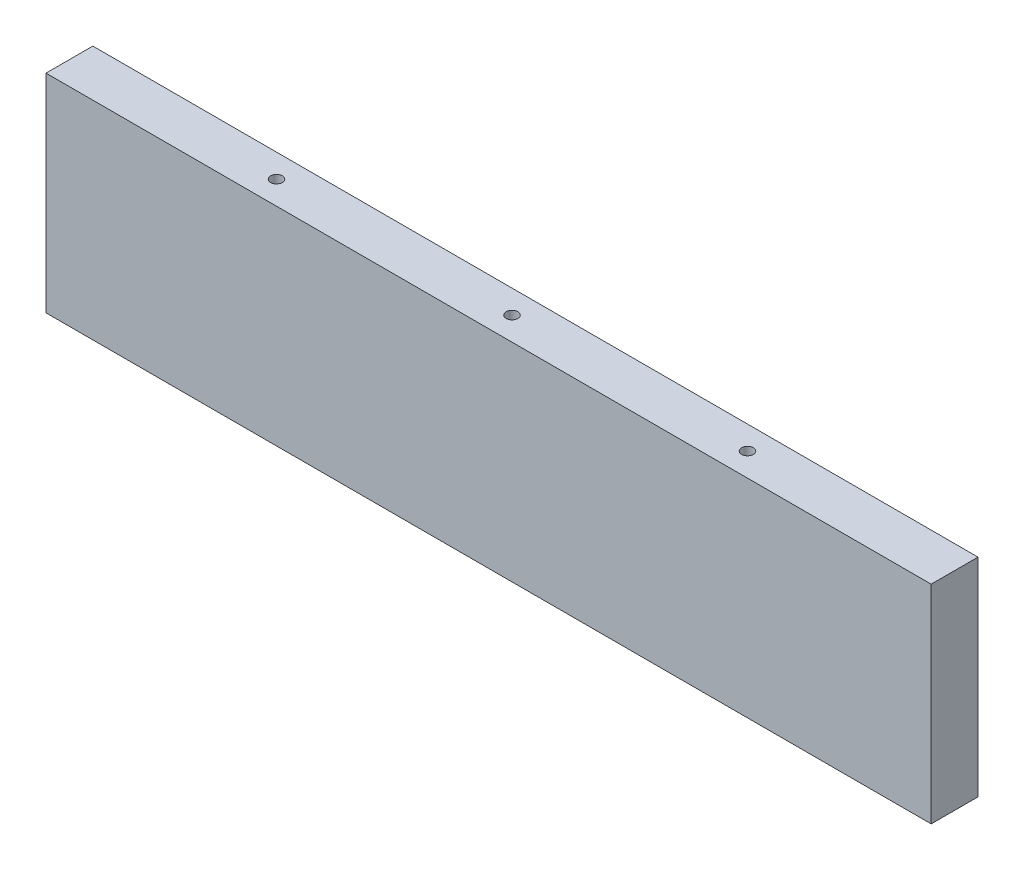
SolidWorks part; units mm, degrees
material "Beech"
ref_plane "Front Plane" through (0, 0, 0) normal (0, 0, 1) x (1, 0, 0)
ref_plane "Top Plane" through (0, 0, 0) normal (0, 1, 0) x (1, 0, 0)
ref_plane "Right Plane" through (0, 0, 0) normal (1, 0, 0) x (0, 0, -1)
sketch "Sketch1" plane through (0, 0, 0) normal (0, 0, 1) x (1, 0, 0)
  line L1 (-16.7045, 12.7) -> (-231.3045, 12.7)
  line L2 (-16.7045, 12.7) -> (-16.7045, 69)
  line L3 (-16.7045, 69) -> (-231.3045, 69)
  line L4 (-231.3045, 12.7) -> (-231.3045, 69)
  line L5 (-16.7045, 12.7) -> (-16.7045, 0) construction
  dimension "D1" = 56.3
extrude "Boss-Extrude1" add sketch "Sketch1" against normal blind 12.7
sketch "Sketch3" plane through (-231.3045, 0, 0) normal (-1, 0, 0) x (0, 0, 1)
  line L4 (0, 12.7) -> (0, 69)
  line L5 (0, 69) -> (-12.7, 69)
  line L6 (-12.7, 69) -> (-12.7, 12.7)
  line L7 (-12.7, 12.7) -> (0, 12.7)
  line L8 (0, 12.7) -> (0, 69)
  line L9 (0, 69) -> (-12.7, 69)
  line L10 (-12.7, 69) -> (-12.7, 12.7)
  line L11 (-12.7, 12.7) -> (0, 12.7)
  dimension "D1" = 0
extrude "Boss-Extrude2" add sketch "Sketch3" along normal blind 12.7
sketch "Sketch4" plane through (-16.7045, 0, 0) normal (1, 0, 0) x (0, 0, -1)
  line L4 (0, 69) -> (0, 12.7)
  line L5 (0, 12.7) -> (12.7, 12.7)
  line L6 (12.7, 12.7) -> (12.7, 69)
  line L7 (12.7, 69) -> (0, 69)
  line L8 (0, 69) -> (0, 12.7)
  line L9 (0, 12.7) -> (12.7, 12.7)
  line L10 (12.7, 12.7) -> (12.7, 69)
  line L11 (12.7, 69) -> (0, 69)
  dimension "D1" = 0
extrude "Boss-Extrude3" add sketch "Sketch4" along normal blind 12.7
hole_wizard "Hole2" positions "Sketch7" profile "Sketch8" legacy
sketch "Sketch7" plane through (-124.0045, 88.05, 66.1243) normal (0, 1, 0) x (1, 0, 0)
  point P15 (-162.3, -97.5257)
  point P34 (-113.65, -38.7424)
  point P36 (-113.65, 13.691)
  point P54 (162.3, -97.5257)
  point P55 (113.65, -38.7424)
  point P56 (113.65, 13.691)
  point P71 (63.85, 72.4743)
  point P73 (0, 72.4743)
  point P74 (-63.85, 72.4743)
sketch "Sketch8" plane through (-286.3045, 88.05, 163.65) normal (1, 0, 0) x (0, 0, 1)
  line L0 (0, 0) -> (0, 32.7039)
  line L1 (0, 32.7039) -> (1.5875, 31.75)
  line L2 (1.5875, 31.75) -> (1.5875, 4.0177)
  line L3 (1.5875, 4.0177) -> (5.08, 0)
  line L4 (5.08, 0) -> (0, 0)
  line L5 (0, -14.3089) -> (0, 102.4216) construction
  line L6 (0, 32.7039) -> (-1.5875, 31.75) construction
  line L7 (-1.5875, 4.0177) -> (-5.08, 0) construction
  dimension "Diameter" = 3.175
  dimension "Depth" = 31.75
  dimension "C-Sink Diameter" = 10.16
  dimension "C-Sink Angle" = 82
  dimension "Drill Angle" = 118
hole_wizard "Hole3" positions "Sketch9" profile "Sketch10" legacy
sketch "Sketch9" plane through (-124.0045, 0, 66.1243) normal (0, -1, 0) x (-1, 0, 0)
  line L1 (0, 465.9538) -> (0, 66.1243) construction
  line L2 (126.073, 146.2179) -> (113.373, 146.2179) construction
  line L6 (119.723, 195.4304) -> (119.723, 97.0054) construction
  line L10 (68.923, 196.0654) -> (68.923, 112.2454) construction
  point P1 (113.65, 39.9076)
  point P3 (113.65, -64.959)
  point P5 (-94.6, 72.4743)
  point P7 (94.6, 72.4743)
  point P9 (0, 72.4743)
  point P11 (0, 104.2243)
  point P13 (0, 351.6538)
  point P15 (0, 213.0704)
  point P17 (40.9792, 213.0704)
  point P19 (166.7958, 213.0704)
  point P21 (207.775, 351.6538)
  point P23 (207.775, 244.1214)
  point P25 (207.775, 136.589)
  point P27 (207.775, 48.5243)
  point P29 (207.775, -78.4757)
  point P33 (-207.775, -78.4757)
  point P34 (-207.775, 48.5243)
  point P35 (-207.775, 136.589)
  point P36 (-207.775, 244.1214)
  point P37 (-207.775, 351.6538)
  point P38 (-166.7958, 213.0704)
  point P39 (-40.9792, 213.0704)
  point P40 (-113.65, -64.959)
  point P41 (-113.65, 39.9076)
  point P65 (119.723, 109.7054)
  point P68 (119.723, 182.7304)
  point P78 (18.123, 109.7054)
  point P79 (18.123, 182.7304)
  point P81 (0, 0)
  point P82 (113.65, 23.941)
  point P83 (0, 0)
  point P84 (207.775, -78.2752)
  point P85 (209.3058, -90.1558)
  point P86 (207.775, -78.4757)
  point P88 (113.65, -64.959)
  point P90 (207.775, 48.5243)
  point P92 (0, 0)
  point P93 (207.775, 136.589)
  point P95 (207.775, 244.1214)
  point P97 (207.775, 351.6538)
  point P99 (113.65, 39.9076)
  point P101 (94.6, 72.4743)
  point P103 (0, 72.4743)
  point P105 (0, 104.2243)
  point P107 (0, 0)
  point P108 (0, 213.0704)
  point P110 (0, 0)
  point P111 (0, 351.6538)
  point P113 (-40.9792, 213.0704)
  point P115 (-94.6, 72.4743)
  point P117 (-166.7958, 213.0704)
  point P119 (-113.65, -64.959)
  point P121 (0, 66.1243)
  point P124 (68.923, 112.2454)
sketch "Sketch10" plane through (-237.6545, 0, 26.2167) normal (1, 0, 0) x (0, 0, -1)
  line L0 (0, 0) -> (0, 32.7039)
  line L1 (0, 32.7039) -> (1.5875, 31.75)
  line L2 (1.5875, 31.75) -> (1.5875, 4.0177)
  line L3 (1.5875, 4.0177) -> (5.08, 0)
  line L4 (5.08, 0) -> (0, 0)
  line L5 (0, -14.3089) -> (0, 102.4216) construction
  line L6 (0, 32.7039) -> (-1.5875, 31.75) construction
  line L7 (-1.5875, 4.0177) -> (-5.08, 0) construction
  dimension "Diameter" = 3.175
  dimension "Depth" = 31.75
  dimension "C-Sink Diameter" = 10.16
  dimension "C-Sink Angle" = 82
  dimension "Drill Angle" = 118
